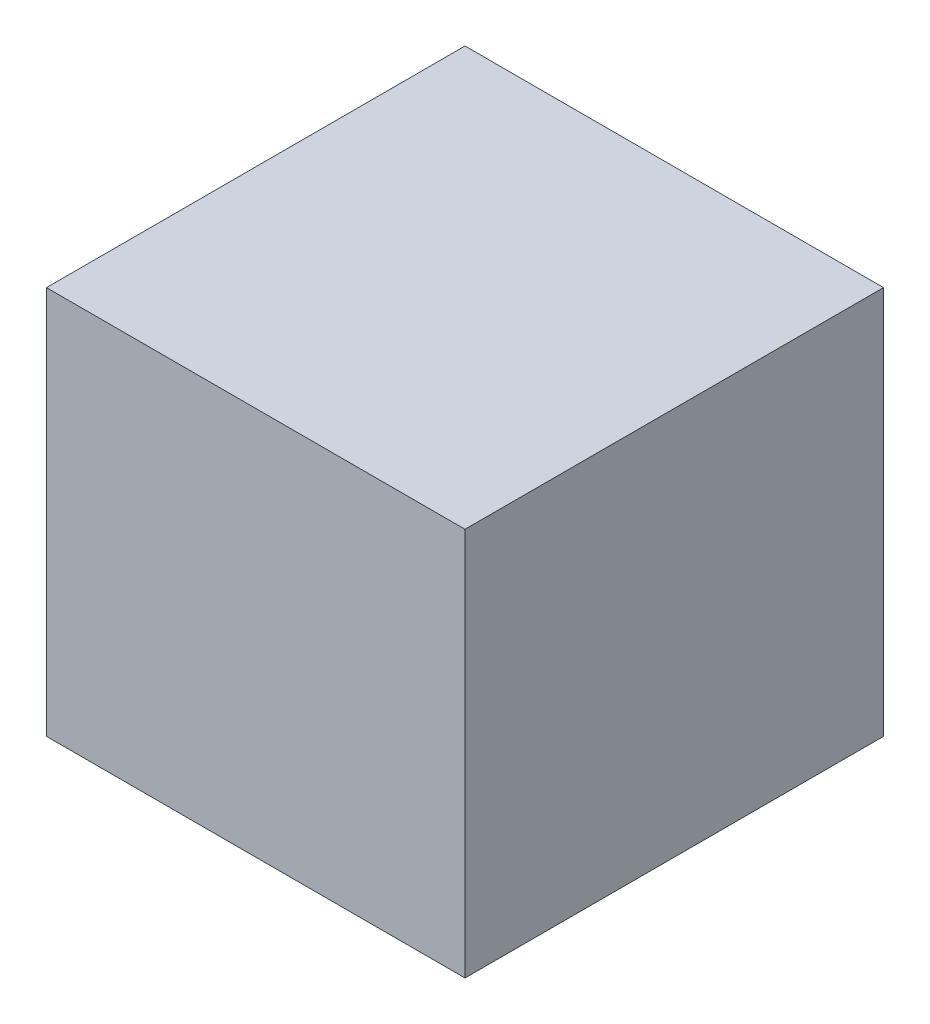
SolidWorks part; units mm, degrees
ref_plane "Plan de face" through (0, 0, 0) normal (0, 0, 1) x (1, 0, 0)
ref_plane "Plan de dessus" through (0, 0, 0) normal (0, 1, 0) x (1, 0, 0)
ref_plane "Plan de droite" through (0, 0, 0) normal (1, 0, 0) x (0, 0, -1)
sketch "Esquisse1" plane through (0, 0, 0) normal (0, 1, 0) x (1, 0, 0)
  line L1 (-21, -21) -> (21, -21)
  line L2 (-21, -21) -> (-21, 21)
  line L3 (-21, 21) -> (21, 21)
  line L4 (21, -21) -> (21, 21)
  line L5 (-21, -21) -> (21, 21) construction
  line L6 (-21, 21) -> (21, -21) construction
  point P0 (0, 0)
  dimension "D1" = 42
  dimension "D2" = 42
extrude "Boss.-Extru.1" add sketch "Esquisse1" along normal blind 39
ref_plane "Plan1" through (0, 39, 0) normal (0, 1, 0) x (1, 0, 0)
sketch "Esquisse3" plane through (0, 39, 0) normal (0, 1, 0) x (1, 0, 0)
  circle A0 centre (0, 0) radius 7.5
  dimension "D1" = 15
